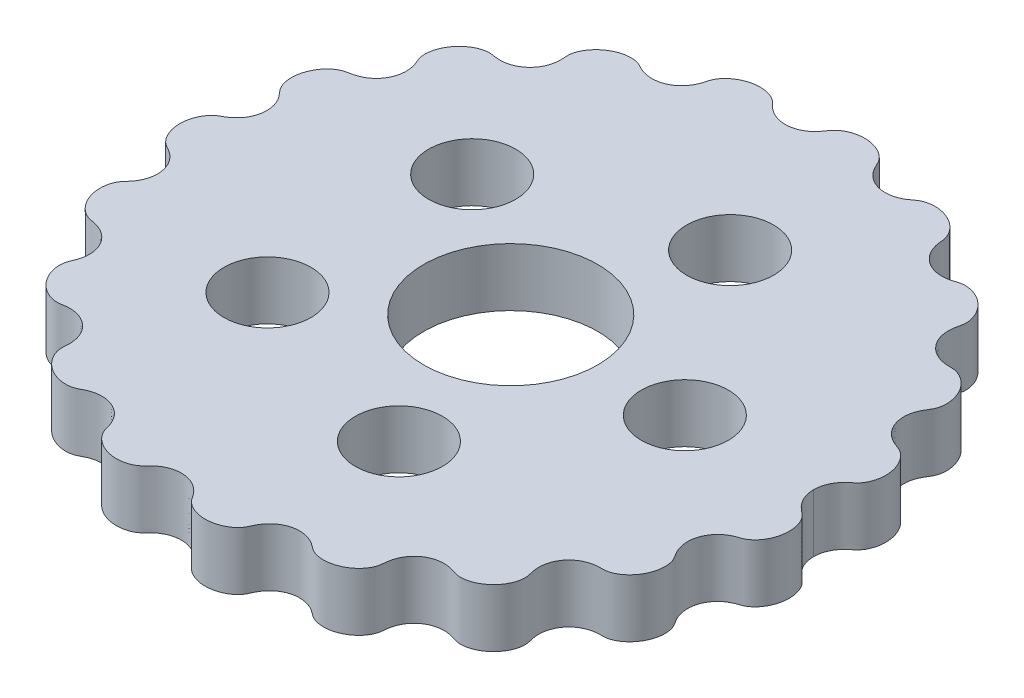
SolidWorks part; units mm, degrees
ref_plane "Front Plane" through (0, 0, 0) normal (0, 0, 1) x (1, 0, 0)
ref_plane "Top Plane" through (0, 0, 0) normal (0, 1, 0) x (1, 0, 0)
ref_plane "Right Plane" through (0, 0, 0) normal (1, 0, 0) x (0, 0, -1)
sketch "Sketch1" plane through (0, 0, 0) normal (0, 1, 0) x (1, 0, 0)
  line L0 (-28.5, 0) -> (26.1, 0) construction
  line L1 (0, 0) -> (-1.2, 0) construction
  line L2 (-1.2, -26.2965) -> (-1.2, 26.2965) construction
  line L3 (0, -27.4748) -> (0, 27.4748) construction
  line L4 (15, 0) -> (16.8, 0)
  line L5 (-1.2, 0) -> (-2.4, 0)
  circle A6 centre (0, 0) radius 7.5
  circle A7 centre (0, 0) radius 15
  circle A8 centre (15, 0) radius 3.75
  circle A9 centre (4.6353, -14.2658) radius 3.75
  circle A10 centre (-12.1353, -8.8168) radius 3.75
  circle A11 centre (-12.1353, 8.8168) radius 3.75
  circle A12 centre (4.6353, 14.2658) radius 3.75
  circle A13 centre (-1.2, 0) radius 30
  circle A14 centre (28.8, 0) radius 2.5
  circle A15 centre (27.3317, -9.2705) radius 2.5
  circle A16 centre (23.0705, -17.6336) radius 2.5
  circle A17 centre (16.4336, -24.2705) radius 2.5
  circle A18 centre (8.0705, -28.5317) radius 2.5
  circle A19 centre (-1.2, -30) radius 2.5
  circle A20 centre (-10.4705, -28.5317) radius 2.5
  circle A21 centre (-18.8336, -24.2705) radius 2.5
  circle A22 centre (-25.4705, -17.6336) radius 2.5
  circle A23 centre (-29.7317, -9.2705) radius 2.5
  circle A24 centre (-31.2, 0) radius 2.5
  circle A25 centre (-29.7317, 9.2705) radius 2.5
  circle A26 centre (-25.4705, 17.6336) radius 2.5
  circle A27 centre (-18.8336, 24.2705) radius 2.5
  circle A28 centre (-10.4705, 28.5317) radius 2.5
  circle A29 centre (-1.2, 30) radius 2.5
  circle A30 centre (8.0705, 28.5317) radius 2.5
  circle A31 centre (16.4336, 24.2705) radius 2.5
  circle A32 centre (23.0705, 17.6336) radius 2.5
  circle A33 centre (27.3317, 9.2705) radius 2.5
  circle A34 centre (-2.4, 0) radius 9.525
  circle A35 centre (-2.4, 0) radius 15
  circle A36 centre (12.6, 0) radius 4
  circle A37 centre (2.2353, -14.2658) radius 4
  circle A38 centre (-14.5353, -8.8168) radius 4
  circle A39 centre (-14.5353, 8.8168) radius 4
  circle A40 centre (2.2353, 14.2658) radius 4
  spline S0 degree 4 poles (26.9104, 6.6012) (26.9742, 6.5637) (27.0975, 6.4823) (27.3266, 6.2942) (27.6183, 5.9575) (27.8831, 5.5093) (28.0722, 4.9735) (28.1608, 4.4391) (28.1609, 3.9238) (28.093, 3.5007) (27.9838, 3.1507) (27.8591, 2.8784) (27.741, 2.6778) (27.605, 2.4959) (27.4503, 2.337) (27.2759, 2.2009) (27.1019, 2.0648) (26.9367, 1.9177) (26.7821, 1.7596) (26.65, 1.601) (26.5385, 1.4453) (26.4457, 1.295) (26.3692, 1.1524) (26.3017, 1.0053) (26.2435, 0.8544) (26.1947, 0.7002) (26.1557, 0.5423) (26.1271, 0.3877) (26.1084, 0.2314) (26.0989, 0.0495) (26.0994, -0.0671) (26.1108, -0.2691) (26.1342, -0.4315) (26.1693, -0.6042) (26.2157, -0.7717) (26.2733, -0.9361) (26.3418, -1.0961) (26.4279, -1.2656) (26.5348, -1.4419) (26.6997, -1.6703) (26.9014, -1.8899) (27.1248, -2.087) (27.3628, -2.2652) (27.5417, -2.4229) (27.6968, -2.6125) (27.831, -2.8239) (27.9427, -3.0552) (28.032, -3.3021) (28.1133, -3.6202) (28.1642, -4.0114) (28.1582, -4.4659) (28.0687, -4.972) (27.9224, -5.3919) (27.7522, -5.7264) (27.5792, -5.9861) (27.4226, -6.1811) (27.2087, -6.3966) (26.9704, -6.5815) (26.7043, -6.7144) (26.4261, -6.8021) (26.2084, -6.8853) (25.996, -6.9818) (25.7924, -7.0957) (25.5065, -7.2884) (25.1668, -7.5959) (24.8233, -8.0656) (24.5731, -8.7228) (24.5132, -9.3741) (24.5959, -9.9089) (24.7329, -10.3062) (24.8635, -10.5783) (24.9836, -10.7878) (25.1181, -10.988) (25.2439, -11.1944) (25.336, -11.4251) (25.3995, -11.6707) (25.4343, -11.9282) (25.442, -12.1937) (25.4188, -12.5249) (25.3424, -12.9166) (25.1912, -13.3478) (24.9449, -13.7987) (24.6361, -14.1974) (24.3194, -14.493) (24.0146, -14.7042) (23.7442, -14.8441) (23.522, -14.9308) (23.2952, -14.9909) (23.0662, -15.0181) (22.8362, -15.0154) (22.6065, -15.0188) (22.3771, -15.0374) (22.15, -15.0735) (21.9017, -15.1343) (21.6364, -15.2275) (21.2852, -15.3974) (20.867, -15.6962) (20.4577, -16.1544) (20.1676, -16.7441) (20.0407, -17.3441) (20.0443, -17.8376) (20.1013, -18.2083) (20.1783, -18.5102) (20.2374, -18.7529) (20.2542, -19.0071) (20.2367, -19.2645) (20.1753, -19.5877) (20.0454, -19.9662) (19.8257, -20.3791) (19.5033, -20.7922) (19.1257, -21.1406) (18.7061, -21.4192) (18.3126, -21.5978) (17.9573, -21.7007) (17.6591, -21.7472) (17.425, -21.7593) (17.197, -21.746) (16.9781, -21.7045) (16.7675, -21.6331) (16.5576, -21.5612) (16.3432, -21.5027) (16.1253, -21.4593) (15.7965, -21.4204) (15.3549, -21.428) (14.789, -21.5503) (14.1546, -21.8806) (13.6662, -22.3459) (13.3364, -22.8823) (13.1735, -23.3537) (13.1046, -23.717) (13.0767, -24.0228) (13.0578, -24.2682) (12.9987, -24.5141) (12.9032, -24.7542) (12.7442, -25.0453) (12.499, -25.369) (12.1557, -25.6963) (11.7049, -25.9946) (11.2116, -26.2122) (10.69, -26.3437) (10.2213, -26.3776) (9.8206, -26.3426) (9.499, -26.2667) (9.2556, -26.1771) (9.0298, -26.0566) (8.8316, -25.9026) (8.5839, -25.7111) (8.2645, -25.511) (7.8101, -25.3123) (7.2055, -25.1928) (6.5502, -25.2287) (5.9713, -25.4243) (5.5369, -25.6878) (5.2457, -25.9387) (5.0554, -26.1438) (4.8999, -26.3482) (4.7746, -26.5455) (4.6646, -26.7519) (4.569, -26.9649) (4.4763, -27.1796) (4.3535, -27.3793) (4.2033, -27.5619) (4.0321, -27.728) (3.7953, -27.9145) (3.4825, -28.1028) (3.0896, -28.2688) (2.605, -28.3883) (2.0954, -28.4312) (1.5735, -28.39) (1.1195, -28.2728) (0.7516, -28.1124) (0.4728, -27.9399) (0.2735, -27.7809) (0.1002, -27.6012) (-0.0369, -27.4007) (-0.1676, -27.1967) (-0.3131, -27.0024) (-0.5125, -26.7738) (-0.8252, -26.4899) (-1.2868, -26.2024) (-1.9065, -26.0034) (-2.5994, -25.9754) (-3.1568, -26.101) (-3.5653, -26.2832) (-3.8534, -26.4638) (-4.0409, -26.6046) (-4.2161, -26.7602) (-4.3804, -26.9272) (-4.5356, -27.1027) (-4.708, -27.2621) (-4.9066, -27.3955) (-5.1223, -27.5066) (-5.3531, -27.5948) (-5.5951, -27.6608) (-5.9041, -27.715) (-6.2804, -27.7366) (-6.7242, -27.7014) (-7.2225, -27.58) (-7.6392, -27.4035) (-7.9745, -27.2016) (-8.2316, -27.0015) (-8.4208, -26.8224) (-8.5884, -26.628) (-8.73, -26.4192) (-8.8438, -26.1979) (-8.9181, -25.9651) (-8.9731, -25.7277) (-9.0439, -25.4943) (-9.1531, -25.2096) (-9.3068, -24.9159) (-9.5135, -24.6237) (-9.8398, -24.2849) (-10.2644, -23.9778) (-10.8297, -23.7381) (-11.4105, -23.6609) (-11.8763, -23.6964) (-12.2188, -23.7735) (-12.4447, -23.8451) (-12.6638, -23.9353) (-12.8761, -24.0403) (-13.082, -24.1572) (-13.2986, -24.2543) (-13.5339, -24.3178) (-13.7805, -24.3538) (-14.0358, -24.3616) (-14.2964, -24.3431) (-14.6185, -24.2887) (-14.9949, -24.1775) (-15.4086, -23.9883) (-15.8372, -23.7006) (-16.1649, -23.3939) (-16.4043, -23.0978) (-16.5733, -22.8298) (-16.6877, -22.6036) (-16.7767, -22.3723) (-16.8377, -22.1385) (-16.8702, -21.9045) (-16.8664, -21.6745) (-16.8432, -21.4462) (-16.8326, -21.2169) (-16.8373, -20.9873) (-16.8603, -20.7588) (-16.9233, -20.4192) (-17.0718, -19.9806) (-17.369, -19.4772) (-17.8749, -18.9885) (-18.448, -18.6772) (-19.0275, -18.5257) (-19.5101, -18.5038) (-19.8766, -18.5383) (-20.1776, -18.5934) (-20.4214, -18.6224) (-20.6712, -18.6091) (-20.9209, -18.565) (-21.1679, -18.4906) (-21.4096, -18.39) (-21.6982, -18.2354) (-22.0201, -18.0093) (-22.351, -17.6983) (-22.6637, -17.2907) (-22.9048, -16.8434) (-23.0478, -16.4273) (-23.1163, -16.0571) (-23.132, -15.7508) (-23.1187, -15.5137) (-23.0797, -15.2858) (-23.0107, -15.072) (-22.918, -14.8679) (-22.8318, -14.6612) (-22.759, -14.4492) (-22.7023, -14.2323) (-22.658, -13.9823) (-22.6359, -13.6994) (-22.6507, -13.3001) (-22.7619, -12.7838) (-23.0293, -12.2149) (-23.4676, -11.712) (-23.9234, -11.3981) (-24.3155, -11.223) (-24.6094, -11.1314) (-24.8495, -11.076) (-25.0926, -11.0387) (-25.3345, -10.9908) (-25.5693, -10.9005) (-25.7937, -10.7797) (-26.006, -10.6307) (-26.2044, -10.4578) (-26.4303, -10.2184) (-26.6648, -9.8998) (-26.879, -9.4996) (-27.0444, -9.0157) (-27.13, -8.5201) (-27.1345, -8.0871) (-27.0849, -7.7198) (-27.006, -7.4259) (-26.9204, -7.2033) (-26.8122, -6.9952) (-26.6786, -6.8073) (-26.5213, -6.6394) (-26.3676, -6.4686) (-26.2255, -6.2877) (-26.0974, -6.0966) (-25.9747, -5.8762) (-25.8647, -5.6245) (-25.7524, -5.2647) (-25.6818, -4.7626) (-25.731, -4.1469) (-25.9619, -3.524) (-26.3213, -3.0106) (-26.6902, -2.673) (-27.001, -2.4627) (-27.2749, -2.314) (-27.4942, -2.1942) (-27.6938, -2.0358) (-27.8724, -1.8494) (-28.0299, -1.6395) (-28.1658, -1.4106) (-28.2784, -1.1691) (-28.3569, -0.9499) (-28.4099, -0.7574) (-28.4448, -0.5945) (-28.4671, -0.4646) (-28.4838, -0.3341) (-28.4949, -0.1942) (-28.5004, -0.0525) (-28.5005, 0.0456) (-28.4955, 0.1802) (-28.4857, 0.3127) (-28.4674, 0.4669) (-28.4356, 0.6491) (-28.3841, 0.8627) (-28.3055, 1.0987) (-28.2068, 1.3282) (-28.0876, 1.5473) (-27.9509, 1.7495) (-27.7973, 1.9316) (-27.6281, 2.0918) (-27.4431, 2.2241) (-27.2427, 2.3305) (-27.0445, 2.4404) (-26.8537, 2.5632) (-26.6725, 2.6998) (-26.4853, 2.8663) (-26.2987, 3.0673) (-26.073, 3.3712) (-25.8526, 3.7999) (-25.7033, 4.3429) (-25.6908, 4.9349) (-25.7972, 5.4631) (-25.983, 5.9142) (-26.1842, 6.2409) (-26.3898, 6.4964) (-26.5384, 6.6564) (-26.611, 6.7378) (-26.647, 6.7788) knots 0 0 0 0 0 0.002514 0.005029 0.010058 0.015086 0.020115 0.024264 0.028413 0.032562 0.034636 0.03671 0.038591 0.040472 0.042353 0.044234 0.046115 0.047995 0.049876 0.051757 0.053134 0.05451 0.055887 0.057263 0.05864 0.060016 0.061393 0.06277 0.064064 0.065358 0.066839 0.06832 0.069801 0.071282 0.072763 0.074244 0.075725 0.077206 0.079231 0.081256 0.085305 0.087329 0.089354 0.091379 0.093403 0.095635 0.097867 0.100099 0.102331 0.106795 0.111259 0.115506 0.119752 0.121875 0.123998 0.126122 0.128245 0.132212 0.134196 0.13618 0.138163 0.140147 0.142131 0.144114 0.149889 0.155664 0.161717 0.167769 0.171876 0.173929 0.175982 0.178036 0.180089 0.182142 0.184196 0.186453 0.18871 0.190968 0.193225 0.19774 0.202255 0.20645 0.210645 0.21484 0.216937 0.219035 0.220991 0.222947 0.224903 0.226859 0.228815 0.230771 0.232727 0.234683 0.237505 0.240328 0.245974 0.252074 0.258174 0.262418 0.266663 0.268785 0.270907 0.27303 0.275152 0.277414 0.279676 0.284201 0.288725 0.29325 0.297435 0.301619 0.305804 0.307896 0.309989 0.311878 0.313768 0.315658 0.317547 0.319437 0.321327 0.323216 0.325106 0.330698 0.336289 0.342722 0.349154 0.353338 0.357522 0.359614 0.361706 0.363798 0.365889 0.368184 0.370478 0.375067 0.379656 0.384245 0.388791 0.393338 0.397884 0.400157 0.40243 0.404563 0.406695 0.408827 0.41096 0.415225 0.41949 0.425619 0.431749 0.437282 0.440049 0.442815 0.444803 0.446791 0.448779 0.450767 0.452755 0.454743 0.456731 0.458718 0.460784 0.462849 0.466979 0.47111 0.47524 0.479777 0.484314 0.488851 0.491119 0.493388 0.495451 0.497514 0.499578 0.501641 0.503704 0.505768 0.509894 0.515977 0.52206 0.527644 0.533228 0.535221 0.537214 0.539208 0.541201 0.543194 0.545187 0.54718 0.549173 0.551306 0.553439 0.555572 0.557704 0.56197 0.566236 0.570665 0.575094 0.577308 0.579523 0.581737 0.583952 0.586026 0.5881 0.590174 0.592248 0.594322 0.596397 0.600545 0.6035 0.606456 0.612367 0.618261 0.624154 0.626169 0.628184 0.630198 0.632213 0.634228 0.636243 0.638257 0.640272 0.642493 0.644714 0.646935 0.649156 0.653597 0.658039 0.662348 0.666657 0.668812 0.670967 0.673121 0.675276 0.677229 0.679181 0.681134 0.683087 0.68504 0.686993 0.688946 0.690899 0.696786 0.702673 0.708614 0.714556 0.718724 0.722892 0.724976 0.72706 0.729144 0.731229 0.733454 0.73568 0.737906 0.740131 0.744583 0.749034 0.753293 0.757552 0.76181 0.76394 0.766069 0.767975 0.769882 0.771788 0.773694 0.775601 0.777507 0.779413 0.78132 0.784235 0.787151 0.792981 0.799177 0.805373 0.809561 0.811656 0.81375 0.815844 0.817939 0.820033 0.822127 0.824365 0.826603 0.828841 0.831079 0.835554 0.84003 0.844223 0.848415 0.852608 0.854705 0.856801 0.858757 0.860713 0.862669 0.864625 0.866581 0.868537 0.870493 0.87245 0.875161 0.877872 0.883295 0.889615 0.895936 0.900182 0.904428 0.906551 0.908674 0.910797 0.912919 0.915183 0.917446 0.919709 0.921972 0.924235 0.925367 0.926498 0.92763 0.928762 0.929893 0.931025 0.932085 0.933146 0.934206 0.935267 0.937388 0.939509 0.94163 0.943751 0.945872 0.947993 0.949922 0.951852 0.953781 0.95571 0.95764 0.959569 0.961498 0.963428 0.966159 0.968891 0.974355 0.979745 0.985135 0.988851 0.992568 0.996284 0.998142 1 1 1 1 1 construction
  spline S1 degree 4 poles (26.1, 0) (26.1, -0.0377) (26.102, -0.1127) (26.1108, -0.2691) (26.1342, -0.4315) (26.1693, -0.6042) (26.2157, -0.7717) (26.2733, -0.9361) (26.3418, -1.0961) (26.4279, -1.2656) (26.5348, -1.4419) (26.6997, -1.6703) (26.9014, -1.8899) (27.1248, -2.087) (27.3628, -2.2652) (27.5417, -2.4229) (27.6968, -2.6125) (27.831, -2.8239) (27.9427, -3.0552) (28.032, -3.3021) (28.1133, -3.6202) (28.1642, -4.0114) (28.1582, -4.4659) (28.0687, -4.972) (27.9224, -5.3919) (27.7522, -5.7264) (27.5792, -5.9861) (27.4226, -6.1811) (27.2087, -6.3966) (26.9704, -6.5815) (26.7043, -6.7144) (26.4261, -6.8021) (26.2084, -6.8853) (25.996, -6.9818) (25.7924, -7.0957) (25.5065, -7.2884) (25.1668, -7.5959) (24.8233, -8.0656) (24.5731, -8.7228) (24.5132, -9.3741) (24.5959, -9.9089) (24.7329, -10.3062) (24.8635, -10.5783) (24.9836, -10.7878) (25.1181, -10.988) (25.2439, -11.1944) (25.336, -11.4251) (25.3995, -11.6707) (25.4343, -11.9282) (25.442, -12.1937) (25.4188, -12.5249) (25.3424, -12.9166) (25.1912, -13.3478) (24.9449, -13.7987) (24.6361, -14.1974) (24.3194, -14.493) (24.0146, -14.7042) (23.7442, -14.8441) (23.522, -14.9308) (23.2952, -14.9909) (23.0662, -15.0181) (22.8362, -15.0154) (22.6065, -15.0188) (22.3771, -15.0374) (22.15, -15.0735) (21.9017, -15.1343) (21.6364, -15.2275) (21.2852, -15.3974) (20.867, -15.6962) (20.4577, -16.1544) (20.1676, -16.7441) (20.0407, -17.3441) (20.0443, -17.8376) (20.1013, -18.2083) (20.1783, -18.5102) (20.2374, -18.7529) (20.2542, -19.0071) (20.2367, -19.2645) (20.1753, -19.5877) (20.0454, -19.9662) (19.8257, -20.3791) (19.5033, -20.7922) (19.1257, -21.1406) (18.7061, -21.4192) (18.3126, -21.5978) (17.9573, -21.7007) (17.6591, -21.7472) (17.425, -21.7593) (17.197, -21.746) (16.9781, -21.7045) (16.7675, -21.6331) (16.5576, -21.5612) (16.3432, -21.5027) (16.1253, -21.4593) (15.7965, -21.4204) (15.3549, -21.428) (14.789, -21.5503) (14.1546, -21.8806) (13.6662, -22.3459) (13.3364, -22.8823) (13.1735, -23.3537) (13.1046, -23.717) (13.0767, -24.0228) (13.0578, -24.2682) (12.9987, -24.5141) (12.9032, -24.7542) (12.7442, -25.0453) (12.499, -25.369) (12.1557, -25.6963) (11.7049, -25.9946) (11.2116, -26.2122) (10.69, -26.3437) (10.2213, -26.3776) (9.8206, -26.3426) (9.499, -26.2667) (9.2556, -26.1771) (9.0298, -26.0566) (8.8316, -25.9026) (8.5839, -25.7111) (8.2645, -25.511) (7.8101, -25.3123) (7.2055, -25.1928) (6.5502, -25.2287) (5.9713, -25.4243) (5.5369, -25.6878) (5.2457, -25.9387) (5.0554, -26.1438) (4.8999, -26.3482) (4.7746, -26.5455) (4.6646, -26.7519) (4.569, -26.9649) (4.4763, -27.1796) (4.3535, -27.3793) (4.2033, -27.5619) (4.0321, -27.728) (3.7953, -27.9145) (3.4825, -28.1028) (3.0896, -28.2688) (2.605, -28.3883) (2.0954, -28.4312) (1.5735, -28.39) (1.1195, -28.2728) (0.7516, -28.1124) (0.4728, -27.9399) (0.2735, -27.7809) (0.1002, -27.6012) (-0.0369, -27.4007) (-0.1676, -27.1967) (-0.3131, -27.0024) (-0.5125, -26.7738) (-0.8252, -26.4899) (-1.2868, -26.2024) (-1.9065, -26.0034) (-2.5994, -25.9754) (-3.1568, -26.101) (-3.5653, -26.2832) (-3.8534, -26.4638) (-4.0409, -26.6046) (-4.2161, -26.7602) (-4.3804, -26.9272) (-4.5356, -27.1027) (-4.708, -27.2621) (-4.9066, -27.3955) (-5.1223, -27.5066) (-5.3531, -27.5948) (-5.5951, -27.6608) (-5.9041, -27.715) (-6.2804, -27.7366) (-6.7242, -27.7014) (-7.2225, -27.58) (-7.6392, -27.4035) (-7.9745, -27.2016) (-8.2316, -27.0015) (-8.4208, -26.8224) (-8.5884, -26.628) (-8.73, -26.4192) (-8.8438, -26.1979) (-8.9181, -25.9651) (-8.9731, -25.7277) (-9.0439, -25.4943) (-9.1531, -25.2096) (-9.3068, -24.9159) (-9.5135, -24.6237) (-9.8398, -24.2849) (-10.2644, -23.9778) (-10.8297, -23.7381) (-11.4105, -23.6609) (-11.8763, -23.6964) (-12.2188, -23.7735) (-12.4447, -23.8451) (-12.6638, -23.9353) (-12.8761, -24.0403) (-13.082, -24.1572) (-13.2986, -24.2543) (-13.5339, -24.3178) (-13.7805, -24.3538) (-14.0358, -24.3616) (-14.2964, -24.3431) (-14.6185, -24.2887) (-14.9949, -24.1775) (-15.4086, -23.9883) (-15.8372, -23.7006) (-16.1649, -23.3939) (-16.4043, -23.0978) (-16.5733, -22.8298) (-16.6877, -22.6036) (-16.7767, -22.3723) (-16.8377, -22.1385) (-16.8702, -21.9045) (-16.8664, -21.6745) (-16.8432, -21.4462) (-16.8326, -21.2169) (-16.8373, -20.9873) (-16.8603, -20.7588) (-16.9233, -20.4192) (-17.0718, -19.9806) (-17.369, -19.4772) (-17.8749, -18.9885) (-18.448, -18.6772) (-19.0275, -18.5257) (-19.5101, -18.5038) (-19.8766, -18.5383) (-20.1776, -18.5934) (-20.4214, -18.6224) (-20.6712, -18.6091) (-20.9209, -18.565) (-21.1679, -18.4906) (-21.4096, -18.39) (-21.6982, -18.2354) (-22.0201, -18.0093) (-22.351, -17.6983) (-22.6637, -17.2907) (-22.9048, -16.8434) (-23.0478, -16.4273) (-23.1163, -16.0571) (-23.132, -15.7508) (-23.1187, -15.5137) (-23.0797, -15.2858) (-23.0107, -15.072) (-22.918, -14.8679) (-22.8318, -14.6612) (-22.759, -14.4492) (-22.7023, -14.2323) (-22.658, -13.9823) (-22.6359, -13.6994) (-22.6507, -13.3001) (-22.7619, -12.7838) (-23.0293, -12.2149) (-23.4676, -11.712) (-23.9234, -11.3981) (-24.3155, -11.223) (-24.6094, -11.1314) (-24.8495, -11.076) (-25.0926, -11.0387) (-25.3345, -10.9908) (-25.5693, -10.9005) (-25.7937, -10.7797) (-26.006, -10.6307) (-26.2044, -10.4578) (-26.4303, -10.2184) (-26.6648, -9.8998) (-26.879, -9.4996) (-27.0444, -9.0157) (-27.13, -8.5201) (-27.1345, -8.0871) (-27.0849, -7.7198) (-27.006, -7.4259) (-26.9204, -7.2033) (-26.8122, -6.9952) (-26.6786, -6.8073) (-26.5213, -6.6394) (-26.3676, -6.4686) (-26.2255, -6.2877) (-26.0974, -6.0966) (-25.9747, -5.8762) (-25.8647, -5.6245) (-25.7524, -5.2647) (-25.6818, -4.7626) (-25.731, -4.1469) (-25.9619, -3.524) (-26.3213, -3.0106) (-26.6902, -2.673) (-27.001, -2.4627) (-27.2749, -2.314) (-27.4942, -2.1942) (-27.6938, -2.0358) (-27.8724, -1.8494) (-28.0299, -1.6395) (-28.1658, -1.4106) (-28.2784, -1.1691) (-28.3569, -0.9499) (-28.4099, -0.7574) (-28.4448, -0.5945) (-28.4671, -0.4646) (-28.4838, -0.3341) (-28.4949, -0.1942) (-28.4991, -0.0862) (-28.5, -0.0288) (-28.5, 0) knots 0.065358 0.065358 0.065358 0.065358 0.065358 0.066839 0.06832 0.069801 0.071282 0.072763 0.074244 0.075725 0.077206 0.079231 0.081256 0.085305 0.087329 0.089354 0.091379 0.093403 0.095635 0.097867 0.100099 0.102331 0.106795 0.111259 0.115506 0.119752 0.121875 0.123998 0.126122 0.128245 0.132212 0.134196 0.13618 0.138163 0.140147 0.142131 0.144114 0.149889 0.155664 0.161717 0.167769 0.171876 0.173929 0.175982 0.178036 0.180089 0.182142 0.184196 0.186453 0.18871 0.190968 0.193225 0.19774 0.202255 0.20645 0.210645 0.21484 0.216937 0.219035 0.220991 0.222947 0.224903 0.226859 0.228815 0.230771 0.232727 0.234683 0.237505 0.240328 0.245974 0.252074 0.258174 0.262418 0.266663 0.268785 0.270907 0.27303 0.275152 0.277414 0.279676 0.284201 0.288725 0.29325 0.297435 0.301619 0.305804 0.307896 0.309989 0.311878 0.313768 0.315658 0.317547 0.319437 0.321327 0.323216 0.325106 0.330698 0.336289 0.342722 0.349154 0.353338 0.357522 0.359614 0.361706 0.363798 0.365889 0.368184 0.370478 0.375067 0.379656 0.384245 0.388791 0.393338 0.397884 0.400157 0.40243 0.404563 0.406695 0.408827 0.41096 0.415225 0.41949 0.425619 0.431749 0.437282 0.440049 0.442815 0.444803 0.446791 0.448779 0.450767 0.452755 0.454743 0.456731 0.458718 0.460784 0.462849 0.466979 0.47111 0.47524 0.479777 0.484314 0.488851 0.491119 0.493388 0.495451 0.497514 0.499578 0.501641 0.503704 0.505768 0.509894 0.515977 0.52206 0.527644 0.533228 0.535221 0.537214 0.539208 0.541201 0.543194 0.545187 0.54718 0.549173 0.551306 0.553439 0.555572 0.557704 0.56197 0.566236 0.570665 0.575094 0.577308 0.579523 0.581737 0.583952 0.586026 0.5881 0.590174 0.592248 0.594322 0.596397 0.600545 0.6035 0.606456 0.612367 0.618261 0.624154 0.626169 0.628184 0.630198 0.632213 0.634228 0.636243 0.638257 0.640272 0.642493 0.644714 0.646935 0.649156 0.653597 0.658039 0.662348 0.666657 0.668812 0.670967 0.673121 0.675276 0.677229 0.679181 0.681134 0.683087 0.68504 0.686993 0.688946 0.690899 0.696786 0.702673 0.708614 0.714556 0.718724 0.722892 0.724976 0.72706 0.729144 0.731229 0.733454 0.73568 0.737906 0.740131 0.744583 0.749034 0.753293 0.757552 0.76181 0.76394 0.766069 0.767975 0.769882 0.771788 0.773694 0.775601 0.777507 0.779413 0.78132 0.784235 0.787151 0.792981 0.799177 0.805373 0.809561 0.811656 0.81375 0.815844 0.817939 0.820033 0.822127 0.824365 0.826603 0.828841 0.831079 0.835554 0.84003 0.844223 0.848415 0.852608 0.854705 0.856801 0.858757 0.860713 0.862669 0.864625 0.866581 0.868537 0.870493 0.87245 0.875161 0.877872 0.883295 0.889615 0.895936 0.900182 0.904428 0.906551 0.908674 0.910797 0.912919 0.915183 0.917446 0.919709 0.921972 0.924235 0.925367 0.926498 0.92763 0.928762 0.929893 0.931025 0.931025 0.931025 0.931025 0.931025
  spline S2 degree 4 poles (26.1, 0) (26.1, 0.0376) (26.102, 0.1124) (26.1108, 0.2685) (26.1342, 0.4303) (26.1693, 0.6027) (26.2157, 0.7697) (26.2733, 0.9336) (26.3417, 1.0932) (26.4279, 1.2622) (26.5346, 1.438) (26.6647, 1.6175) (26.8202, 1.7972) (26.9901, 1.9633) (27.1709, 2.1172) (27.3596, 2.2614) (27.5347, 2.4225) (27.6873, 2.6133) (27.8194, 2.8254) (27.9294, 3.0568) (28.0174, 3.3035) (28.0973, 3.6212) (28.1472, 4.0116) (28.1407, 4.4663) (28.0507, 4.9735) (27.8829, 5.455) (27.6715, 5.843) (27.4436, 6.1449) (27.2267, 6.3648) (27.0409, 6.5166) (26.8436, 6.6432) (26.6359, 6.7382) (26.4199, 6.8111) (26.2069, 6.8919) (25.9995, 6.9866) (25.7999, 7.097) (25.5146, 7.2869) (25.172, 7.593) (24.8251, 8.0632) (24.573, 8.723) (24.5135, 9.3751) (24.5967, 9.9085) (24.7339, 10.3046) (24.8642, 10.5762) (24.9838, 10.7853) (25.1166, 10.986) (25.2378, 11.1945) (25.3267, 11.4258) (25.3878, 11.6713) (25.4209, 11.9285) (25.4273, 12.1933) (25.4029, 12.5237) (25.3257, 12.9142) (25.174, 13.3453) (24.9269, 13.7973) (24.6164, 14.1978) (24.297, 14.4955) (23.9896, 14.7081) (23.7185, 14.8479) (23.4979, 14.934) (23.2747, 14.9937) (23.0513, 15.0227) (22.8265, 15.0238) (22.6021, 15.0278) (22.378, 15.046) (22.1559, 15.0804) (21.8286, 15.1585) (21.4093, 15.3223) (20.9247, 15.6352) (20.4568, 16.1578) (20.1669, 16.7485) (20.041, 17.3471) (20.0453, 17.8394) (20.1023, 18.2092) (20.1778, 18.5107) (20.2318, 18.7541) (20.2449, 19.0078) (20.2252, 19.2644) (20.1746, 19.5212) (20.0962, 19.7748) (19.9675, 20.0808) (19.7692, 20.427) (19.4884, 20.786) (19.1123, 21.133) (18.6951, 21.411) (18.3044, 21.5899) (17.9516, 21.6944) (17.5971, 21.7522) (17.3027, 21.7613) (17.0135, 21.7242) (16.7419, 21.6352) (16.5255, 21.5634) (16.3045, 21.5051) (16.08, 21.4631) (15.8308, 21.4372) (15.5583, 21.4348) (15.1861, 21.4722) (14.6961, 21.6037) (14.1458, 21.8923) (13.6634, 22.3528) (13.3351, 22.8883) (13.1733, 23.3588) (13.1047, 23.7212) (13.0759, 24.0263) (13.0525, 24.2707) (12.9895, 24.515) (12.8921, 24.7535) (12.7313, 25.0427) (12.4854, 25.3645) (12.1419, 25.6899) (11.6909, 25.9876) (11.1964, 26.2054) (10.6723, 26.3373) (10.2003, 26.3711) (9.7968, 26.3356) (9.4748, 26.2593) (9.233, 26.1706) (9.01, 26.0529) (8.8137, 25.9055) (8.5704, 25.7195) (8.2582, 25.5237) (7.8094, 25.325) (7.2073, 25.202) (6.5461, 25.2353) (5.8772, 25.4622) (5.3986, 25.786) (5.085, 26.1055) (4.8853, 26.3742) (4.7666, 26.5637) (4.6617, 26.7612) (4.5693, 26.9645) (4.4773, 27.1684) (4.3594, 27.359) (4.2144, 27.5373) (4.0466, 27.7027) (3.8098, 27.8925) (3.4925, 28.0862) (3.093, 28.2569) (2.6024, 28.3789) (2.0891, 28.4226) (1.566, 28.382) (1.1127, 28.2662) (0.7451, 28.1078) (0.4658, 27.9376) (0.2655, 27.7808) (0.0903, 27.6039) (-0.0506, 27.4068) (-0.1822, 27.204) (-0.3275, 27.0102) (-0.5264, 26.7821) (-0.838, 26.4986) (-1.2981, 26.2111) (-1.9184, 26.0114) (-2.6145, 25.984) (-3.1735, 26.1125) (-3.582, 26.2979) (-3.8673, 26.4791) (-4.0499, 26.6174) (-4.2212, 26.7695) (-4.3819, 26.9324) (-4.5359, 27.1018) (-4.7063, 27.2554) (-4.9021, 27.3863) (-5.1165, 27.4966) (-5.3472, 27.5851) (-5.5911, 27.6519) (-5.9024, 27.7067) (-6.2817, 27.7289) (-6.73, 27.6934) (-7.2343, 27.5702) (-7.6563, 27.3905) (-7.9967, 27.1843) (-8.2563, 26.9795) (-8.4483, 26.7967) (-8.6511, 26.5554) (-8.817, 26.2938) (-8.9134, 26.0392) (-8.9701, 25.8124) (-9.0327, 25.5873) (-9.1257, 25.31) (-9.3159, 24.91) (-9.6747, 24.4361) (-10.1835, 24.0258) (-10.8362, 23.7471) (-11.4204, 23.6699) (-11.885, 23.7058) (-12.2267, 23.7831) (-12.452, 23.8548) (-12.6708, 23.9446) (-12.8827, 24.0491) (-13.0896, 24.1633) (-13.3076, 24.2559) (-13.543, 24.3166) (-13.7894, 24.3504) (-14.0442, 24.3567) (-14.3041, 24.337) (-14.6252, 24.2816) (-15.0005, 24.1698) (-15.413, 23.9806) (-15.8407, 23.6936) (-16.2143, 23.3448) (-16.485, 22.9926) (-16.6692, 22.6601) (-16.7825, 22.3711) (-16.8455, 22.1383) (-16.8805, 21.9053) (-16.8813, 21.6757) (-16.8608, 21.4476) (-16.8506, 21.2188) (-16.8554, 20.9897) (-16.8782, 20.7616) (-16.9407, 20.4228) (-17.0884, 19.9851) (-17.3858, 19.4807) (-17.8945, 18.9905) (-18.4699, 18.6811) (-18.9904, 18.5487) (-19.4065, 18.5188) (-19.706, 18.5311) (-19.9442, 18.558) (-20.1802, 18.5992) (-20.4191, 18.6236) (-20.6652, 18.6099) (-20.9131, 18.5657) (-21.1602, 18.4916) (-21.4036, 18.3903) (-21.6943, 18.2349) (-22.0185, 18.0074) (-22.3518, 17.6944) (-22.6668, 17.2838) (-22.9095, 16.8332) (-23.0533, 16.4139) (-23.122, 16.0408) (-23.1375, 15.7333) (-23.1242, 15.4968) (-23.0858, 15.2707) (-23.0198, 15.0593) (-22.9309, 14.8568) (-22.847, 14.6525) (-22.7758, 14.4431) (-22.7201, 14.2291) (-22.6612, 13.8972) (-22.6444, 13.4427) (-22.7419, 12.8653) (-23.0456, 12.2192) (-23.4424, 11.7647) (-23.8363, 11.4753) (-24.161, 11.3062) (-24.3884, 11.2127) (-24.6231, 11.1398) (-24.8625, 11.0843) (-25.1048, 11.0455) (-25.3451, 10.9926) (-25.5781, 10.8996) (-25.8009, 10.7771) (-26.0117, 10.6271) (-26.2088, 10.4536) (-26.4333, 10.2139) (-26.6665, 9.8956) (-26.8796, 9.4961) (-27.0447, 9.0134) (-27.1306, 8.5189) (-27.1361, 8.0869) (-27.0881, 7.7202) (-27.0111, 7.4265) (-26.9274, 7.2037) (-26.8215, 6.9951) (-26.6914, 6.8052) (-26.5372, 6.635) (-26.3844, 6.4641) (-26.2428, 6.2834) (-26.1149, 6.0928) (-25.9923, 5.8728) (-25.8823, 5.6218) (-25.77, 5.2629) (-25.699, 4.7597) (-25.7493, 4.1408) (-25.9834, 3.518) (-26.345, 3.0082) (-26.7118, 2.6756) (-27.016, 2.4701) (-27.2831, 2.3232) (-27.4957, 2.2024) (-27.6915, 2.0453) (-27.8687, 1.86) (-28.0262, 1.6502) (-28.1632, 1.4198) (-28.2767, 1.1768) (-28.3557, 0.9562) (-28.4092, 0.7624) (-28.4443, 0.5985) (-28.4668, 0.4676) (-28.4836, 0.3363) (-28.4949, 0.1958) (-28.4991, 0.0868) (-28.5, 0.029) (-28.5, 0) knots 0.065429 0.065429 0.065429 0.065429 0.065429 0.066909 0.06839 0.06987 0.071351 0.072832 0.074312 0.075793 0.077274 0.079299 0.081323 0.083348 0.085373 0.087398 0.089423 0.091448 0.093473 0.095705 0.097936 0.100168 0.1024 0.106864 0.111328 0.115615 0.119903 0.124191 0.126335 0.128478 0.130422 0.132365 0.134309 0.136252 0.138195 0.140139 0.142082 0.144026 0.149879 0.155733 0.161783 0.167834 0.17194 0.173994 0.176047 0.1781 0.180154 0.182207 0.184261 0.186518 0.188775 0.191032 0.193289 0.197803 0.202317 0.206554 0.210791 0.215028 0.217147 0.219265 0.221181 0.223096 0.225012 0.226928 0.228843 0.230759 0.232675 0.23459 0.240315 0.24604 0.252138 0.258236 0.26248 0.266724 0.268846 0.270968 0.273091 0.275213 0.277474 0.279736 0.281998 0.28426 0.288783 0.293307 0.297478 0.30165 0.305822 0.307907 0.309993 0.313887 0.315834 0.317781 0.319728 0.321675 0.323622 0.325569 0.328265 0.330961 0.336353 0.342782 0.349211 0.353395 0.357579 0.35967 0.361762 0.363854 0.365946 0.36824 0.370534 0.375121 0.379709 0.384296 0.388885 0.393473 0.398062 0.400356 0.40265 0.404741 0.406832 0.408922 0.411013 0.415194 0.419375 0.425582 0.43179 0.437484 0.443178 0.445084 0.44699 0.448896 0.450802 0.452707 0.454613 0.456519 0.458425 0.460533 0.46264 0.466855 0.471071 0.475286 0.479822 0.484358 0.488895 0.491163 0.493431 0.495494 0.497557 0.499621 0.501684 0.503747 0.505811 0.509937 0.516018 0.522099 0.527761 0.533424 0.535376 0.537328 0.539281 0.541233 0.543185 0.545137 0.547089 0.549041 0.551195 0.55335 0.555504 0.557658 0.561967 0.566275 0.570786 0.575296 0.577551 0.579806 0.582061 0.584316 0.588304 0.590297 0.591294 0.592291 0.596278 0.600266 0.606335 0.612404 0.618295 0.624187 0.626202 0.628218 0.630233 0.632248 0.634263 0.636278 0.638293 0.640308 0.642529 0.64475 0.646971 0.649191 0.653633 0.658074 0.662384 0.666693 0.671002 0.673157 0.675311 0.677265 0.679218 0.681171 0.683124 0.685077 0.68703 0.688983 0.690936 0.696822 0.702707 0.708727 0.714747 0.718834 0.720878 0.722922 0.724965 0.727009 0.729053 0.731096 0.733342 0.735588 0.737834 0.74008 0.744572 0.749064 0.753364 0.757665 0.761965 0.764115 0.766265 0.76815 0.770035 0.771919 0.773804 0.775689 0.777574 0.779458 0.781343 0.787178 0.793013 0.799206 0.805399 0.807494 0.809588 0.811682 0.813777 0.815871 0.817965 0.82006 0.822154 0.824391 0.826629 0.828866 0.831104 0.835579 0.840053 0.844247 0.84844 0.852634 0.854731 0.856827 0.858784 0.86074 0.862697 0.864654 0.86661 0.868567 0.870523 0.87248 0.875191 0.877902 0.883324 0.889723 0.896121 0.900285 0.904449 0.906531 0.908613 0.910695 0.912776 0.91506 0.917343 0.919626 0.92191 0.924193 0.925335 0.926476 0.927618 0.92876 0.929901 0.931043 0.931043 0.931043 0.931043 0.931043
  spline S3 degree 4 poles (-28.5, 0) (-28.5, -0.0377) (-28.502, -0.1127) (-28.5108, -0.2691) (-28.5342, -0.4315) (-28.5693, -0.6042) (-28.6157, -0.7717) (-28.6733, -0.9361) (-28.7418, -1.0961) (-28.8279, -1.2656) (-28.9348, -1.4419) (-29.0997, -1.6703) (-29.3014, -1.8899) (-29.5248, -2.087) (-29.7628, -2.2652) (-29.9417, -2.4229) (-30.0968, -2.6125) (-30.231, -2.8239) (-30.3427, -3.0552) (-30.432, -3.3021) (-30.5133, -3.6202) (-30.5642, -4.0114) (-30.5582, -4.4659) (-30.4687, -4.972) (-30.3224, -5.3919) (-30.1522, -5.7264) (-29.9792, -5.9861) (-29.8226, -6.1811) (-29.6087, -6.3966) (-29.3704, -6.5815) (-29.1043, -6.7144) (-28.8261, -6.8021) (-28.6084, -6.8853) (-28.396, -6.9818) (-28.1924, -7.0957) (-27.9065, -7.2884) (-27.5668, -7.5959) (-27.2233, -8.0656) (-26.9731, -8.7228) (-26.9132, -9.3741) (-26.9959, -9.9089) (-27.1329, -10.3062) (-27.2635, -10.5783) (-27.3836, -10.7878) (-27.5181, -10.988) (-27.6439, -11.1944) (-27.736, -11.4251) (-27.7995, -11.6707) (-27.8343, -11.9282) (-27.842, -12.1937) (-27.8188, -12.5249) (-27.7424, -12.9166) (-27.5912, -13.3478) (-27.3449, -13.7987) (-27.0361, -14.1974) (-26.7194, -14.493) (-26.4146, -14.7042) (-26.1442, -14.8441) (-25.922, -14.9308) (-25.6952, -14.9909) (-25.4662, -15.0181) (-25.2362, -15.0154) (-25.0065, -15.0188) (-24.7771, -15.0374) (-24.55, -15.0735) (-24.3017, -15.1343) (-24.0364, -15.2275) (-23.6852, -15.3974) (-23.267, -15.6962) (-22.8577, -16.1544) (-22.5676, -16.7441) (-22.4407, -17.3441) (-22.4443, -17.8376) (-22.5013, -18.2083) (-22.5783, -18.5102) (-22.6374, -18.7529) (-22.6542, -19.0071) (-22.6367, -19.2645) (-22.5753, -19.5877) (-22.4454, -19.9662) (-22.2257, -20.3791) (-21.9033, -20.7922) (-21.5257, -21.1406) (-21.1061, -21.4192) (-20.7126, -21.5978) (-20.3573, -21.7007) (-20.0591, -21.7472) (-19.825, -21.7593) (-19.597, -21.746) (-19.3781, -21.7045) (-19.1675, -21.6331) (-18.9576, -21.5612) (-18.7432, -21.5027) (-18.5253, -21.4593) (-18.1965, -21.4204) (-17.7549, -21.428) (-17.189, -21.5503) (-16.5546, -21.8806) (-16.0662, -22.3459) (-15.7364, -22.8823) (-15.5735, -23.3537) (-15.5046, -23.717) (-15.4767, -24.0228) (-15.4578, -24.2682) (-15.3987, -24.5141) (-15.3032, -24.7542) (-15.1442, -25.0453) (-14.899, -25.369) (-14.5557, -25.6963) (-14.1049, -25.9946) (-13.6116, -26.2122) (-13.09, -26.3437) (-12.6213, -26.3776) (-12.2206, -26.3426) (-11.899, -26.2667) (-11.6556, -26.1771) (-11.4298, -26.0566) (-11.2316, -25.9026) (-10.9839, -25.7111) (-10.6645, -25.511) (-10.2101, -25.3123) (-9.6055, -25.1928) (-8.9502, -25.2287) (-8.3713, -25.4243) (-7.9369, -25.6878) (-7.6457, -25.9387) (-7.4554, -26.1438) (-7.2999, -26.3482) (-7.1746, -26.5455) (-7.0646, -26.7519) (-6.969, -26.9649) (-6.8763, -27.1796) (-6.7535, -27.3793) (-6.6033, -27.5619) (-6.4321, -27.728) (-6.1953, -27.9145) (-5.8825, -28.1028) (-5.4896, -28.2688) (-5.005, -28.3883) (-4.4954, -28.4312) (-3.9735, -28.39) (-3.5195, -28.2728) (-3.1516, -28.1124) (-2.8728, -27.9399) (-2.6735, -27.7809) (-2.5002, -27.6012) (-2.3631, -27.4007) (-2.2324, -27.1967) (-2.0869, -27.0024) (-1.8875, -26.7738) (-1.5748, -26.4899) (-1.1132, -26.2024) (-0.4935, -26.0034) (0.1994, -25.9754) (0.7568, -26.101) (1.1653, -26.2832) (1.4534, -26.4638) (1.6409, -26.6046) (1.8161, -26.7602) (1.9804, -26.9272) (2.1356, -27.1027) (2.308, -27.2621) (2.5066, -27.3955) (2.7223, -27.5066) (2.9531, -27.5948) (3.1951, -27.6608) (3.5041, -27.715) (3.8804, -27.7366) (4.3242, -27.7014) (4.8225, -27.58) (5.2392, -27.4035) (5.5745, -27.2016) (5.8316, -27.0015) (6.0208, -26.8224) (6.1884, -26.628) (6.33, -26.4192) (6.4438, -26.1979) (6.5181, -25.9651) (6.5731, -25.7277) (6.6439, -25.4943) (6.7531, -25.2096) (6.9068, -24.9159) (7.1135, -24.6237) (7.4398, -24.2849) (7.8644, -23.9778) (8.4297, -23.7381) (9.0105, -23.6609) (9.4763, -23.6964) (9.8188, -23.7735) (10.0447, -23.8451) (10.2638, -23.9353) (10.4761, -24.0403) (10.682, -24.1572) (10.8986, -24.2543) (11.1339, -24.3178) (11.3805, -24.3538) (11.6358, -24.3616) (11.8964, -24.3431) (12.2185, -24.2887) (12.5949, -24.1775) (13.0086, -23.9883) (13.4372, -23.7006) (13.7649, -23.3939) (14.0043, -23.0978) (14.1733, -22.8298) (14.2877, -22.6036) (14.3767, -22.3723) (14.4377, -22.1385) (14.4702, -21.9045) (14.4664, -21.6745) (14.4432, -21.4462) (14.4326, -21.2169) (14.4373, -20.9873) (14.4603, -20.7588) (14.5233, -20.4192) (14.6718, -19.9806) (14.969, -19.4772) (15.4749, -18.9885) (16.048, -18.6772) (16.6275, -18.5257) (17.1101, -18.5038) (17.4766, -18.5383) (17.7776, -18.5934) (18.0214, -18.6224) (18.2712, -18.6091) (18.5209, -18.565) (18.7679, -18.4906) (19.0096, -18.39) (19.2982, -18.2354) (19.6201, -18.0093) (19.951, -17.6983) (20.2637, -17.2907) (20.5048, -16.8434) (20.6478, -16.4273) (20.7163, -16.0571) (20.732, -15.7508) (20.7187, -15.5137) (20.6797, -15.2858) (20.6107, -15.072) (20.518, -14.8679) (20.4318, -14.6612) (20.359, -14.4492) (20.3023, -14.2323) (20.258, -13.9823) (20.2359, -13.6994) (20.2507, -13.3001) (20.3619, -12.7838) (20.6293, -12.2149) (21.0676, -11.712) (21.5234, -11.3981) (21.9155, -11.223) (22.2094, -11.1314) (22.4495, -11.076) (22.6926, -11.0387) (22.9345, -10.9908) (23.1693, -10.9005) (23.3937, -10.7797) (23.606, -10.6307) (23.8044, -10.4578) (24.0303, -10.2184) (24.2648, -9.8998) (24.479, -9.4996) (24.6444, -9.0157) (24.73, -8.5201) (24.7345, -8.0871) (24.6849, -7.7198) (24.606, -7.4259) (24.5204, -7.2033) (24.4122, -6.9952) (24.2786, -6.8073) (24.1213, -6.6394) (23.9676, -6.4686) (23.8255, -6.2877) (23.6974, -6.0966) (23.5747, -5.8762) (23.4647, -5.6245) (23.3524, -5.2647) (23.2818, -4.7626) (23.331, -4.1469) (23.5619, -3.524) (23.9213, -3.0106) (24.2902, -2.673) (24.601, -2.4627) (24.8749, -2.314) (25.0942, -2.1942) (25.2938, -2.0358) (25.4724, -1.8494) (25.6299, -1.6395) (25.7658, -1.4106) (25.8784, -1.1691) (25.9569, -0.9499) (26.0099, -0.7574) (26.0448, -0.5945) (26.0671, -0.4646) (26.0838, -0.3341) (26.0949, -0.1942) (26.0991, -0.0862) (26.1, -0.0288) (26.1, 0) knots 0.065358 0.065358 0.065358 0.065358 0.065358 0.066839 0.06832 0.069801 0.071282 0.072763 0.074244 0.075725 0.077206 0.079231 0.081256 0.085305 0.087329 0.089354 0.091379 0.093403 0.095635 0.097867 0.100099 0.102331 0.106795 0.111259 0.115506 0.119752 0.121875 0.123998 0.126122 0.128245 0.132212 0.134196 0.13618 0.138163 0.140147 0.142131 0.144114 0.149889 0.155664 0.161717 0.167769 0.171876 0.173929 0.175982 0.178036 0.180089 0.182142 0.184196 0.186453 0.18871 0.190968 0.193225 0.19774 0.202255 0.20645 0.210645 0.21484 0.216937 0.219035 0.220991 0.222947 0.224903 0.226859 0.228815 0.230771 0.232727 0.234683 0.237505 0.240328 0.245974 0.252074 0.258174 0.262418 0.266663 0.268785 0.270907 0.27303 0.275152 0.277414 0.279676 0.284201 0.288725 0.29325 0.297435 0.301619 0.305804 0.307896 0.309989 0.311878 0.313768 0.315658 0.317547 0.319437 0.321327 0.323216 0.325106 0.330698 0.336289 0.342722 0.349154 0.353338 0.357522 0.359614 0.361706 0.363798 0.365889 0.368184 0.370478 0.375067 0.379656 0.384245 0.388791 0.393338 0.397884 0.400157 0.40243 0.404563 0.406695 0.408827 0.41096 0.415225 0.41949 0.425619 0.431749 0.437282 0.440049 0.442815 0.444803 0.446791 0.448779 0.450767 0.452755 0.454743 0.456731 0.458718 0.460784 0.462849 0.466979 0.47111 0.47524 0.479777 0.484314 0.488851 0.491119 0.493388 0.495451 0.497514 0.499578 0.501641 0.503704 0.505768 0.509894 0.515977 0.52206 0.527644 0.533228 0.535221 0.537214 0.539208 0.541201 0.543194 0.545187 0.54718 0.549173 0.551306 0.553439 0.555572 0.557704 0.56197 0.566236 0.570665 0.575094 0.577308 0.579523 0.581737 0.583952 0.586026 0.5881 0.590174 0.592248 0.594322 0.596397 0.600545 0.6035 0.606456 0.612367 0.618261 0.624154 0.626169 0.628184 0.630198 0.632213 0.634228 0.636243 0.638257 0.640272 0.642493 0.644714 0.646935 0.649156 0.653597 0.658039 0.662348 0.666657 0.668812 0.670967 0.673121 0.675276 0.677229 0.679181 0.681134 0.683087 0.68504 0.686993 0.688946 0.690899 0.696786 0.702673 0.708614 0.714556 0.718724 0.722892 0.724976 0.72706 0.729144 0.731229 0.733454 0.73568 0.737906 0.740131 0.744583 0.749034 0.753293 0.757552 0.76181 0.76394 0.766069 0.767975 0.769882 0.771788 0.773694 0.775601 0.777507 0.779413 0.78132 0.784235 0.787151 0.792981 0.799177 0.805373 0.809561 0.811656 0.81375 0.815844 0.817939 0.820033 0.822127 0.824365 0.826603 0.828841 0.831079 0.835554 0.84003 0.844223 0.848415 0.852608 0.854705 0.856801 0.858757 0.860713 0.862669 0.864625 0.866581 0.868537 0.870493 0.87245 0.875161 0.877872 0.883295 0.889615 0.895936 0.900182 0.904428 0.906551 0.908674 0.910797 0.912919 0.915183 0.917446 0.919709 0.921972 0.924235 0.925367 0.926498 0.92763 0.928762 0.929893 0.931025 0.931025 0.931025 0.931025 0.931025
  spline S4 degree 4 poles (-28.5, 0) (-28.5, 0.0376) (-28.502, 0.1124) (-28.5108, 0.2685) (-28.5342, 0.4303) (-28.5693, 0.6027) (-28.6157, 0.7697) (-28.6733, 0.9336) (-28.7417, 1.0932) (-28.8279, 1.2622) (-28.9346, 1.438) (-29.0647, 1.6175) (-29.2202, 1.7972) (-29.3901, 1.9633) (-29.5709, 2.1172) (-29.7596, 2.2614) (-29.9347, 2.4225) (-30.0873, 2.6133) (-30.2194, 2.8254) (-30.3294, 3.0568) (-30.4174, 3.3035) (-30.4973, 3.6212) (-30.5472, 4.0116) (-30.5407, 4.4663) (-30.4507, 4.9735) (-30.2829, 5.455) (-30.0715, 5.843) (-29.8436, 6.1449) (-29.6267, 6.3648) (-29.4409, 6.5166) (-29.2436, 6.6432) (-29.0359, 6.7382) (-28.8199, 6.8111) (-28.6069, 6.8919) (-28.3995, 6.9866) (-28.1999, 7.097) (-27.9146, 7.2869) (-27.572, 7.593) (-27.2251, 8.0632) (-26.973, 8.723) (-26.9135, 9.3751) (-26.9967, 9.9085) (-27.1339, 10.3046) (-27.2642, 10.5762) (-27.3838, 10.7853) (-27.5166, 10.986) (-27.6378, 11.1945) (-27.7267, 11.4258) (-27.7878, 11.6713) (-27.8209, 11.9285) (-27.8273, 12.1933) (-27.8029, 12.5237) (-27.7257, 12.9142) (-27.574, 13.3453) (-27.3269, 13.7973) (-27.0164, 14.1978) (-26.697, 14.4955) (-26.3896, 14.7081) (-26.1185, 14.8479) (-25.8979, 14.934) (-25.6747, 14.9937) (-25.4513, 15.0227) (-25.2265, 15.0238) (-25.0021, 15.0278) (-24.778, 15.046) (-24.5559, 15.0804) (-24.2286, 15.1585) (-23.8093, 15.3223) (-23.3247, 15.6352) (-22.8568, 16.1578) (-22.5669, 16.7485) (-22.441, 17.3471) (-22.4453, 17.8394) (-22.5023, 18.2092) (-22.5778, 18.5107) (-22.6318, 18.7541) (-22.6449, 19.0078) (-22.6252, 19.2644) (-22.5746, 19.5212) (-22.4962, 19.7748) (-22.3675, 20.0808) (-22.1692, 20.427) (-21.8884, 20.786) (-21.5123, 21.133) (-21.0951, 21.411) (-20.7044, 21.5899) (-20.3516, 21.6944) (-19.9971, 21.7522) (-19.7027, 21.7613) (-19.4135, 21.7242) (-19.1419, 21.6352) (-18.9255, 21.5634) (-18.7045, 21.5051) (-18.48, 21.4631) (-18.2308, 21.4372) (-17.9583, 21.4348) (-17.5861, 21.4722) (-17.0961, 21.6037) (-16.5458, 21.8923) (-16.0634, 22.3528) (-15.7351, 22.8883) (-15.5733, 23.3588) (-15.5047, 23.7212) (-15.4759, 24.0263) (-15.4525, 24.2707) (-15.3895, 24.515) (-15.2921, 24.7535) (-15.1313, 25.0427) (-14.8854, 25.3645) (-14.5419, 25.6899) (-14.0909, 25.9876) (-13.5964, 26.2054) (-13.0723, 26.3373) (-12.6003, 26.3711) (-12.1968, 26.3356) (-11.8748, 26.2593) (-11.633, 26.1706) (-11.41, 26.0529) (-11.2137, 25.9055) (-10.9704, 25.7195) (-10.6582, 25.5237) (-10.2094, 25.325) (-9.6073, 25.202) (-8.9461, 25.2353) (-8.2772, 25.4622) (-7.7986, 25.786) (-7.485, 26.1055) (-7.2853, 26.3742) (-7.1666, 26.5637) (-7.0617, 26.7612) (-6.9693, 26.9645) (-6.8773, 27.1684) (-6.7594, 27.359) (-6.6144, 27.5373) (-6.4466, 27.7027) (-6.2098, 27.8925) (-5.8925, 28.0862) (-5.493, 28.2569) (-5.0024, 28.3789) (-4.4891, 28.4226) (-3.966, 28.382) (-3.5127, 28.2662) (-3.1451, 28.1078) (-2.8658, 27.9376) (-2.6655, 27.7808) (-2.4903, 27.6039) (-2.3494, 27.4068) (-2.2178, 27.204) (-2.0725, 27.0102) (-1.8736, 26.7821) (-1.562, 26.4986) (-1.1019, 26.2111) (-0.4816, 26.0114) (0.2145, 25.984) (0.7735, 26.1125) (1.182, 26.2979) (1.4673, 26.4791) (1.6499, 26.6174) (1.8212, 26.7695) (1.9819, 26.9324) (2.1359, 27.1018) (2.3063, 27.2554) (2.5021, 27.3863) (2.7165, 27.4966) (2.9472, 27.5851) (3.1911, 27.6519) (3.5024, 27.7067) (3.8817, 27.7289) (4.33, 27.6934) (4.8343, 27.5702) (5.2563, 27.3905) (5.5967, 27.1843) (5.8563, 26.9795) (6.0483, 26.7967) (6.2511, 26.5554) (6.417, 26.2938) (6.5134, 26.0392) (6.5701, 25.8124) (6.6327, 25.5873) (6.7257, 25.31) (6.9159, 24.91) (7.2747, 24.4361) (7.7835, 24.0258) (8.4362, 23.7471) (9.0204, 23.6699) (9.485, 23.7058) (9.8267, 23.7831) (10.052, 23.8548) (10.2708, 23.9446) (10.4827, 24.0491) (10.6896, 24.1633) (10.9076, 24.2559) (11.143, 24.3166) (11.3894, 24.3504) (11.6442, 24.3567) (11.9041, 24.337) (12.2252, 24.2816) (12.6005, 24.1698) (13.013, 23.9806) (13.4407, 23.6936) (13.8143, 23.3448) (14.085, 22.9926) (14.2692, 22.6601) (14.3825, 22.3711) (14.4455, 22.1383) (14.4805, 21.9053) (14.4813, 21.6757) (14.4608, 21.4476) (14.4506, 21.2188) (14.4554, 20.9897) (14.4782, 20.7616) (14.5407, 20.4228) (14.6884, 19.9851) (14.9858, 19.4807) (15.4945, 18.9905) (16.0699, 18.6811) (16.5904, 18.5487) (17.0065, 18.5188) (17.306, 18.5311) (17.5442, 18.558) (17.7802, 18.5992) (18.0191, 18.6236) (18.2652, 18.6099) (18.5131, 18.5657) (18.7602, 18.4916) (19.0036, 18.3903) (19.2943, 18.2349) (19.6185, 18.0074) (19.9518, 17.6944) (20.2668, 17.2838) (20.5095, 16.8332) (20.6533, 16.4139) (20.722, 16.0408) (20.7375, 15.7333) (20.7242, 15.4968) (20.6858, 15.2707) (20.6198, 15.0593) (20.5309, 14.8568) (20.447, 14.6525) (20.3758, 14.4431) (20.3201, 14.2291) (20.2612, 13.8972) (20.2444, 13.4427) (20.3419, 12.8653) (20.6456, 12.2192) (21.0424, 11.7647) (21.4363, 11.4753) (21.761, 11.3062) (21.9884, 11.2127) (22.2231, 11.1398) (22.4625, 11.0843) (22.7048, 11.0455) (22.9451, 10.9926) (23.1781, 10.8996) (23.4009, 10.7771) (23.6117, 10.6271) (23.8088, 10.4536) (24.0333, 10.2139) (24.2665, 9.8956) (24.4796, 9.4961) (24.6447, 9.0134) (24.7306, 8.5189) (24.7361, 8.0869) (24.6881, 7.7202) (24.6111, 7.4265) (24.5274, 7.2037) (24.4215, 6.9951) (24.2914, 6.8052) (24.1372, 6.635) (23.9844, 6.4641) (23.8428, 6.2834) (23.7149, 6.0928) (23.5923, 5.8728) (23.4823, 5.6218) (23.37, 5.2629) (23.299, 4.7597) (23.3493, 4.1408) (23.5834, 3.518) (23.945, 3.0082) (24.3118, 2.6756) (24.616, 2.4701) (24.8831, 2.3232) (25.0957, 2.2024) (25.2915, 2.0453) (25.4687, 1.86) (25.6262, 1.6502) (25.7632, 1.4198) (25.8767, 1.1768) (25.9557, 0.9562) (26.0092, 0.7624) (26.0443, 0.5985) (26.0668, 0.4676) (26.0836, 0.3363) (26.0949, 0.1958) (26.0991, 0.0868) (26.1, 0.029) (26.1, 0) knots 0.065429 0.065429 0.065429 0.065429 0.065429 0.066909 0.06839 0.06987 0.071351 0.072832 0.074312 0.075793 0.077274 0.079299 0.081323 0.083348 0.085373 0.087398 0.089423 0.091448 0.093473 0.095705 0.097936 0.100168 0.1024 0.106864 0.111328 0.115615 0.119903 0.124191 0.126335 0.128478 0.130422 0.132365 0.134309 0.136252 0.138195 0.140139 0.142082 0.144026 0.149879 0.155733 0.161783 0.167834 0.17194 0.173994 0.176047 0.1781 0.180154 0.182207 0.184261 0.186518 0.188775 0.191032 0.193289 0.197803 0.202317 0.206554 0.210791 0.215028 0.217147 0.219265 0.221181 0.223096 0.225012 0.226928 0.228843 0.230759 0.232675 0.23459 0.240315 0.24604 0.252138 0.258236 0.26248 0.266724 0.268846 0.270968 0.273091 0.275213 0.277474 0.279736 0.281998 0.28426 0.288783 0.293307 0.297478 0.30165 0.305822 0.307907 0.309993 0.313887 0.315834 0.317781 0.319728 0.321675 0.323622 0.325569 0.328265 0.330961 0.336353 0.342782 0.349211 0.353395 0.357579 0.35967 0.361762 0.363854 0.365946 0.36824 0.370534 0.375121 0.379709 0.384296 0.388885 0.393473 0.398062 0.400356 0.40265 0.404741 0.406832 0.408922 0.411013 0.415194 0.419375 0.425582 0.43179 0.437484 0.443178 0.445084 0.44699 0.448896 0.450802 0.452707 0.454613 0.456519 0.458425 0.460533 0.46264 0.466855 0.471071 0.475286 0.479822 0.484358 0.488895 0.491163 0.493431 0.495494 0.497557 0.499621 0.501684 0.503747 0.505811 0.509937 0.516018 0.522099 0.527761 0.533424 0.535376 0.537328 0.539281 0.541233 0.543185 0.545137 0.547089 0.549041 0.551195 0.55335 0.555504 0.557658 0.561967 0.566275 0.570786 0.575296 0.577551 0.579806 0.582061 0.584316 0.588304 0.590297 0.591294 0.592291 0.596278 0.600266 0.606335 0.612404 0.618295 0.624187 0.626202 0.628218 0.630233 0.632248 0.634263 0.636278 0.638293 0.640308 0.642529 0.64475 0.646971 0.649191 0.653633 0.658074 0.662384 0.666693 0.671002 0.673157 0.675311 0.677265 0.679218 0.681171 0.683124 0.685077 0.68703 0.688983 0.690936 0.696822 0.702707 0.708727 0.714747 0.718834 0.720878 0.722922 0.724965 0.727009 0.729053 0.731096 0.733342 0.735588 0.737834 0.74008 0.744572 0.749064 0.753364 0.757665 0.761965 0.764115 0.766265 0.76815 0.770035 0.771919 0.773804 0.775689 0.777574 0.779458 0.781343 0.787178 0.793013 0.799206 0.805399 0.807494 0.809588 0.811682 0.813777 0.815871 0.817965 0.82006 0.822154 0.824391 0.826629 0.828866 0.831104 0.835579 0.840053 0.844247 0.84844 0.852634 0.854731 0.856827 0.858784 0.86074 0.862697 0.864654 0.86661 0.868567 0.870523 0.87248 0.875191 0.877902 0.883324 0.889723 0.896121 0.900285 0.904449 0.906531 0.908613 0.910695 0.912776 0.91506 0.917343 0.919626 0.92191 0.924193 0.925335 0.926476 0.927618 0.92876 0.929901 0.931043 0.931043 0.931043 0.931043 0.931043
  point P9 (-1.2, 0)
  point P14 (0, 0)
  point P31 (0, 0)
  dimension "D1" = 5
  dimension "D2" = 60
  dimension "D3" = 15
  dimension "D4" = 30
  dimension "D5" = 7.5
  dimension "D8" = 19.05
  dimension "D9" = 30
  dimension "D10" = 5
  dimension "D6" = 5
  dimension "D7" = 20
extrude "Boss-Extrude1" add sketch "Sketch1" along normal blind 5 from offset 0.5 contours S2 S1 | A10 | A9 | A8 | A12 | A11 | A6
